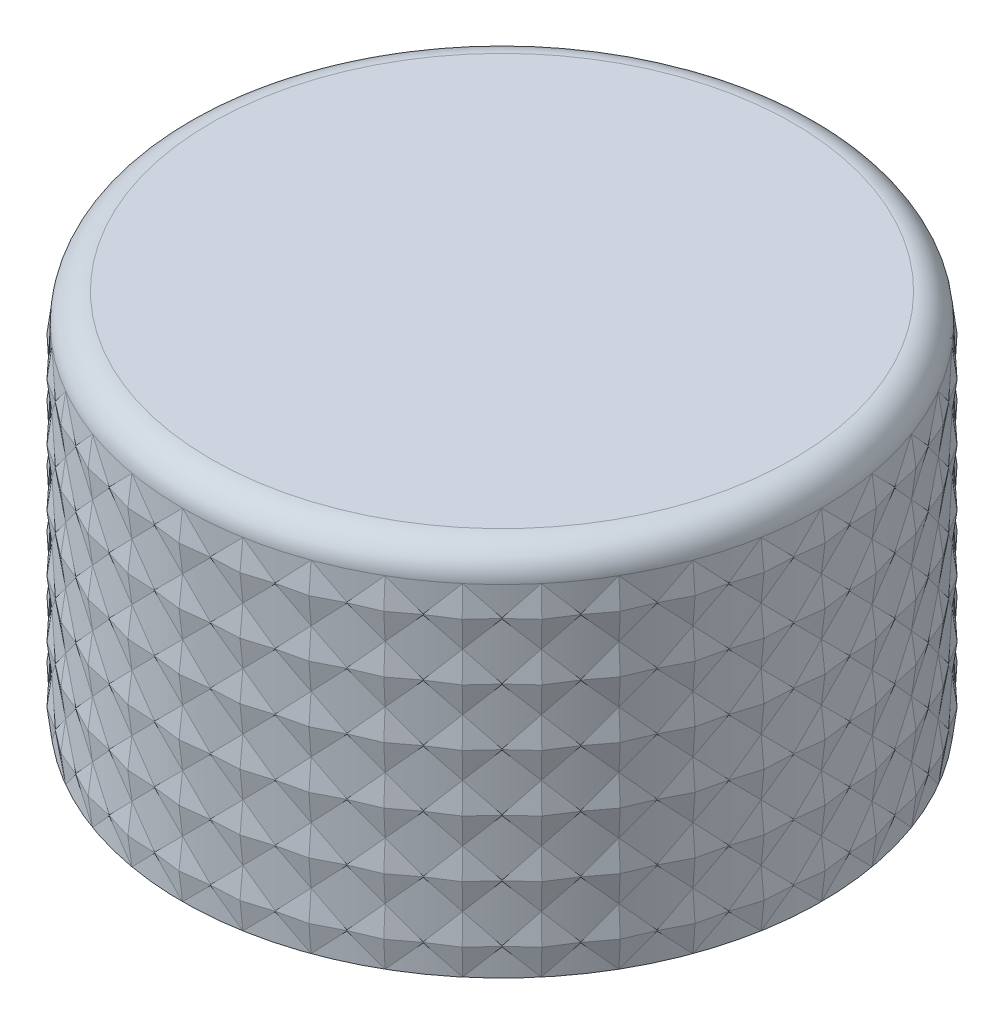
SolidWorks part; units mm, degrees
ref_plane "Front Plane" through (0, 0, 0) normal (0, 0, 1) x (1, 0, 0)
ref_plane "Top Plane" through (0, 0, 0) normal (0, 1, 0) x (1, 0, 0)
ref_plane "Right Plane" through (0, 0, 0) normal (1, 0, 0) x (0, 0, -1)
sketch "Sketch4" plane through (0, 0, 0) normal (0, 1, 0) x (1, 0, 0)
  circle A0 centre (0, 0) radius 11.25
extrude "Boss-Extrude4" add sketch "Sketch4" along normal blind 13
sketch "Sketch5" plane through (0, 0, 0) normal (0, 1, 0) x (1, 0, 0)
  circle A0 centre (0, 0) radius 9
  circle A1 centre (0, 0) radius 4
extrude "Cut-Extrude2" cut sketch "Sketch5" along normal blind 12
sketch "Sketch6" plane through (0, 0, 0) normal (0, -1, 0) x (1, 0, 0)
  circle A0 centre (0, 0) radius 3.1
extrude "Cut-Extrude3" cut sketch "Sketch6" against normal blind 5
sketch "Sketch7" plane through (0, 0, 0) normal (0, -1, 0) x (1, 0, 0)
  circle A0 centre (0, 0) radius 4
extrude "Cut-Extrude4" cut sketch "Sketch7" against normal blind 2
sketch "Sketch9" plane through (0, 0, 0) normal (0, -1, 0) x (1, 0, 0)
  line L0 (0, -3.1) -> (0, 1.45) construction
  line L1 (0, 1.45) -> (2.74, 1.45)
  line L2 (2.74, 1.45) -> (0, 1.45)
  line L3 (0, 1.45) -> (-2.74, 1.45)
  circle A0 centre (0, 0) radius 3.1 construction
  circle A1 centre (0, 0) radius 3.1 construction
  circle A2 centre (0, 0) radius 3.1
extrude "Cut-Extrude5" cut sketch "Sketch9" against normal blind 12 contours A2 L0 L3 | L0 A2 L1
sketch "Sketch10" plane through (0, 0, 0) normal (0, -1, 0) x (1, 0, 0)
  line L0 (0, 0) -> (0, 11.25)
  circle A0 centre (0, 0) radius 11.25 construction
ref_plane "Plane1" through (0, 0, 11.25) normal (0, 0, 1) x (1, 0, 0)
fillet "Fillet2" radius 1 1 edges at (0, 13, 11.25)
sketch "Sketch12" plane through (0, 0, 11.25) normal (0, 0, 1) x (1, 0, 0)
  line L0 (0, 12) -> (0, 11)
  line L1 (-11.25, 12) -> (11.25, 12) construction
  line L2 (0, 10) -> (1, 11)
  line L3 (0, 10) -> (-1, 11)
  line L4 (1, 11) -> (0, 12)
  line L5 (-1, 11) -> (0, 12)
  line L6 (0, 10) -> (0, 12) construction
  line L7 (1, 11) -> (-1, 11) construction
  line L8 (0, 10) -> (0, 9)
  line L9 (0, 8) -> (1, 9)
  line L10 (0, 8) -> (-1, 9)
  line L11 (1, 9) -> (0, 10)
  line L12 (-1, 9) -> (0, 10)
  line L13 (0, 8) -> (0, 10) construction
  line L14 (1, 9) -> (-1, 9) construction
  line L15 (0, 8) -> (0, 7)
  line L16 (0, 6) -> (1, 7)
  line L17 (0, 6) -> (-1, 7)
  line L18 (1, 7) -> (0, 8)
  line L19 (-1, 7) -> (0, 8)
  line L20 (0, 6) -> (0, 8) construction
  line L21 (1, 7) -> (-1, 7) construction
  line L22 (0, 6) -> (0, 5)
  line L23 (0, 4) -> (1, 5)
  line L24 (0, 4) -> (-1, 5)
  line L25 (1, 5) -> (0, 6)
  line L26 (-1, 5) -> (0, 6)
  line L27 (0, 4) -> (0, 6) construction
  line L28 (1, 5) -> (-1, 5) construction
  line L29 (0, 4) -> (0, 3)
  line L30 (0, 2) -> (1, 3)
  line L31 (0, 2) -> (-1, 3)
  line L32 (1, 3) -> (0, 4)
  line L33 (-1, 3) -> (0, 4)
  line L34 (0, 2) -> (0, 4) construction
  line L35 (1, 3) -> (-1, 3) construction
  line L36 (0, 2) -> (0, 1)
  line L37 (0, 0) -> (1, 1)
  line L38 (0, 0) -> (-1, 1)
  line L39 (1, 1) -> (0, 2)
  line L40 (-1, 1) -> (0, 2)
  line L41 (0, 0) -> (0, 2) construction
  line L42 (1, 1) -> (-1, 1) construction
  dimension "D1" = 6
extrude "Boss-Extrude6" add sketch "Sketch12" along normal blind 1 draft 80 separate body
pattern_circular "CirPattern5" count 36 over 360 about axis through (0, 0, 0) along (0, 1, 0) of "Boss-Extrude6"
